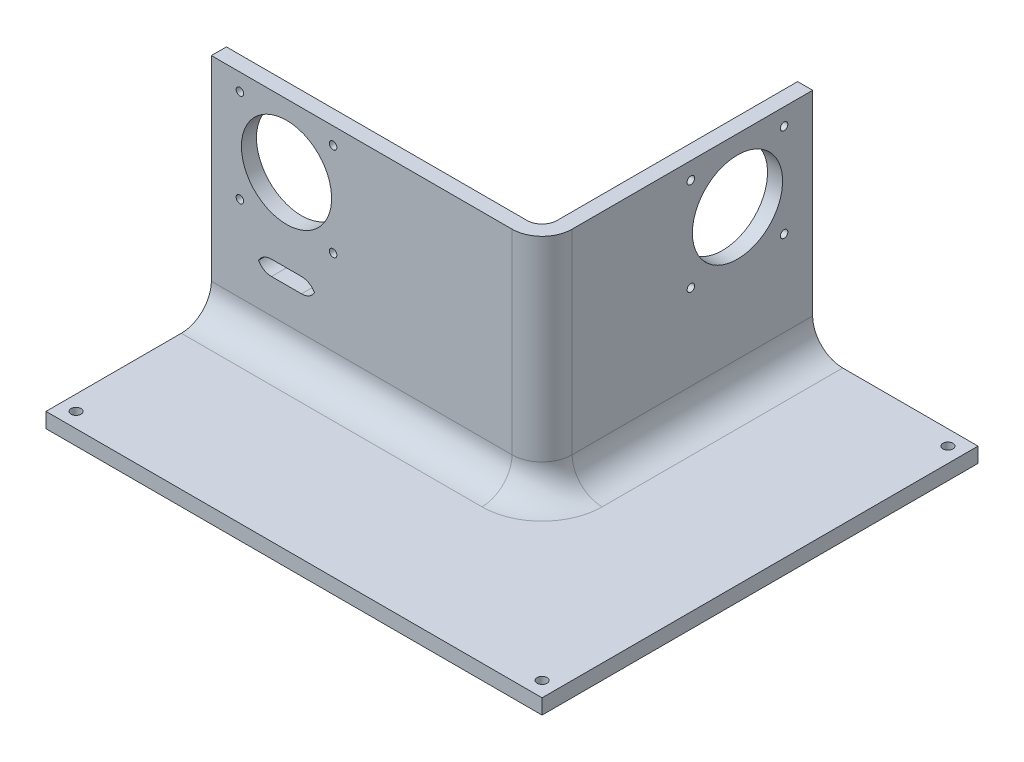
SolidWorks part; units mm, degrees
ref_plane "Front Plane" through (0, 0, 0) normal (0, 0, 1) x (1, 0, 0)
ref_plane "Top Plane" through (0, 0, 0) normal (0, 1, 0) x (1, 0, 0)
ref_plane "Right Plane" through (0, 0, 0) normal (1, 0, 0) x (0, 0, -1)
sketch "Sketch1" plane through (0, 0, 0) normal (0, 1, 0) x (1, 0, 0)
  line L0 (0, 85) -> (0, 0)
  line L1 (-105, -85) -> (105, -85)
  line L2 (-105, -85) -> (-105, 85)
  line L3 (-105, 85) -> (105, 85)
  line L4 (105, -85) -> (105, 85)
  line L5 (-105, -85) -> (105, 85) construction
  line L6 (-105, 85) -> (105, -85) construction
  line L7 (0, 0) -> (-105, 0)
  line L8 (-105, 0) -> (-105, -85)
  point P0 (0, 0)
  dimension "D1" = 170
  dimension "D2" = 210
extrude "Boss-Extrude1" add sketch "Sketch1" along normal blind 20 contours L0 L7 L2 L1 L4 L3 region at (17.5, 0, 14.1667)
sketch "Sketch2" plane through (0, 20, 0) normal (0, 1, 0) x (1, 0, 0)
  line L0 (0, 85) -> (105, 85) construction
  line L1 (0, 0) -> (5, 0)
  line L2 (0, 0) -> (0, 85)
  line L3 (0, 85) -> (5, 85)
  line L4 (5, 0) -> (5, 85)
  line L5 (0, 0) -> (5, 85) construction
  line L6 (0, 85) -> (5, 0) construction
  line L7 (0, 0) -> (-105, 0) construction
  line L8 (0, 85) -> (0, 0) construction
  point P0 (2.5, 42.5)
  dimension "D1" = 0
  dimension "D2" = 0
  dimension "D3" = 0
  dimension "D4" = 5
extrude "Boss-Extrude2" add sketch "Sketch2" along normal blind 60
sketch "Sketch3" plane through (0, 0, 0) normal (-1, 0, 0) x (0, 0, 1)
  line L0 (-85, 80) -> (0, 80) construction
  line L1 (-85, 80) -> (-85, 0) construction
  circle A0 centre (-60, 58.85) radius 15
  dimension "D3" = 30
  dimension "D1" = 21.15
  dimension "D2" = 25
extrude "Cut-Extrude1" cut sketch "Sketch3" against normal blind 100
sketch "Sketch4" plane through (0, 0, 0) normal (-1, 0, 0) x (0, 0, 1)
  circle A4 centre (-75.5, 74.35) radius 1.25
  circle A5 centre (-44.5, 74.35) radius 1.25
  circle A6 centre (-75.5, 43.35) radius 1.25
  circle A7 centre (-44.5, 43.35) radius 1.25
  circle A8 centre (-60, 58.85) radius 15 construction
  dimension "D1" = 0
  dimension "D3" = 0
  dimension "D6" = 2.5
  dimension "D9" = 2.5
  dimension "D12" = 0
  dimension "D7" = 2.5
  dimension "D8" = 2.5
  dimension "D10" = 15.5
  dimension "D2" = 31
  dimension "D4" = 31
  dimension "D5" = 31
  dimension "D11" = 15.5
extrude "Cut-Extrude2" cut sketch "Sketch4" against normal blind 100
sketch "Sketch7" plane through (0, 20, 0) normal (0, 1, 0) x (1, 0, 0)
  line L1 (-105, 0) -> (5, 0)
  line L2 (-105, 0) -> (-105, -5)
  line L3 (-105, -5) -> (5, -5)
  line L4 (5, 0) -> (5, -5)
  dimension "D1" = 5
  dimension "D2" = 0
extrude "Boss-Extrude6" add sketch "Sketch7" along normal blind 60
ref_plane "Plane2" through (-0.4878, 0, 0.6098) normal (-0.6247, 0, 0.7809) x (0.7809, 0, 0.6247)
fillet "Fillet3" radius 5 1 edges at (0, 40, 0)
sketch "Sketch8" plane through (0, 20, 0) normal (0, 1, 0) x (1, 0, 0)
  line L0 (-105, -85) -> (105, -85) construction
  line L1 (80, -85) -> (105, -85)
  line L2 (80, -85) -> (80, 85)
  line L3 (80, 85) -> (105, 85)
  line L4 (105, -85) -> (105, 85)
  line L5 (80, -85) -> (105, 85) construction
  line L6 (80, 85) -> (105, -85) construction
  line L7 (105, -60) -> (-105, -60)
  line L8 (105, -60) -> (105, -85)
  line L9 (105, -85) -> (-105, -85)
  line L10 (-105, -60) -> (-105, -85)
  line L11 (105, -60) -> (-105, -85) construction
  line L12 (105, -85) -> (-105, -60) construction
  point P0 (92.5, 0)
  point P6 (0, -72.5)
  line M7 (-105, -5) -> (-105, -85)
  line M8 (-105, -85) -> (105, -85)
  line M9 (105, -85) -> (105, 85)
  line M10 (105, 85) -> (5, 85)
  dimension "D1" = 0
  dimension "D2" = 0
  dimension "D3" = 25
  dimension "D4" = 25
extrude "Cut-Extrude3" cut sketch "Sketch8" against normal blind 100 contours L7 L4 L2 M10 | L7 L2 M9 M8 | L2 L7 M7 M8 region at (92.5, 20, 72.5) region at (-12.5, 20, 72.5) region at (92.5, 20, -12.5)
sketch "Sketch9" plane through (0, 20, 0) normal (0, 1, 0) x (1, 0, 0)
  line L0 (80, -60) -> (80, 85) construction
  line L1 (5, 85) -> (80, 85) construction
  line L2 (80, -60) -> (-105, -60) construction
  line L4 (-105, -60) -> (-105, -5) construction
  circle A0 centre (55, 80) radius 1.65
  circle A1 centre (55, -55) radius 1.65
  circle A2 centre (-100, -55) radius 1.65
  dimension "D3" = 3.3
  dimension "D6" = 3.3
  dimension "D8" = 3.3
  dimension "D1" = 25
  dimension "D2" = 5
  dimension "D4" = 0
  dimension "D5" = 5
  dimension "D7" = 0
  dimension "D9" = 5
extrude "Cut-Extrude4" cut sketch "Sketch9" against normal blind 100
sketch "Sketch10" plane through (0, 20, 0) normal (0, 1, 0) x (1, 0, 0)
  line L0 (-105, -5) -> (5, -5) construction
  line L1 (80, -60) -> (5, -60)
  line L2 (80, -60) -> (80, 85)
  line L3 (80, 85) -> (5, 85)
  line L4 (5, -60) -> (5, 85)
  line L5 (80, -60) -> (5, 85) construction
  line L6 (80, 85) -> (5, -60) construction
  line L7 (80, -5) -> (-105, -5)
  line L8 (80, -5) -> (80, -60)
  line L9 (80, -60) -> (-105, -60)
  line L10 (-105, -5) -> (-105, -60)
  line L11 (80, -5) -> (-105, -60) construction
  line L12 (80, -60) -> (-105, -5) construction
  line L13 (80, -60) -> (80, 85) construction
  point P0 (42.5, 12.5)
  point P6 (-12.5, -32.5)
  dimension "D1" = 0
  dimension "D2" = 0
  dimension "D3" = 0
  dimension "D4" = 0
extrude "Cut-Extrude5" cut sketch "Sketch10" against normal blind 15 contours L2 L1 L4 L3 | L8 L7 L10 L9
fillet "Fillet4" radius 10 3 edges at (5, 42.5, 5) (-50, 5, 5) (5, 5, -40)
sketch "Sketch11" plane through (0, 0, 5) normal (0, 0, 1) x (1, 0, 0)
  line L0 (-105, 80) -> (-105, 0) construction
  line L1 (-90, 26.35) -> (-70, 26.35)
  line L2 (-90, 26.35) -> (-90, 31.35)
  line L3 (-90, 31.35) -> (-70, 31.35)
  line L4 (-70, 26.35) -> (-70, 31.35)
  line L5 (-90, 26.35) -> (-70, 31.35) construction
  line L6 (-90, 31.35) -> (-70, 26.35) construction
  line L7 (-5, 0) -> (-105, 0) construction
  point P0 (-80, 28.85)
  point P9 (-47.5, 28.85)
  dimension "D1" = 25
  dimension "D2" = 28.85
  dimension "D3" = 5
  dimension "D4" = 20
extrude "Cut-Extrude6" cut sketch "Sketch11" against normal blind 6
fillet "Fillet5" radius 5 4 edges at (-90, 26.35, 2.5) (-90, 31.35, 2.5) (-70, 31.35, 2.5) (-70, 26.35, 2.5)
sketch "Sketch12" plane through (0, 0, 0) normal (0, 0, -1) x (-1, 0, 0)
  line L2 (5, 80) -> (105, 80) construction
  line L3 (105, 80) -> (105, 0) construction
  circle A0 centre (80, 58.85) radius 15
  circle A1 centre (95.5, 74.35) radius 1.25
  circle A2 centre (64.5, 74.35) radius 1.25
  circle A3 centre (64.5, 43.35) radius 1.25
  circle A4 centre (95.5, 43.35) radius 1.25
  dimension "D1" = 30
  dimension "D10" = 2.5
  dimension "D11" = 2.5
  dimension "D12" = 2.5
  dimension "D13" = 2.5
  dimension "D2" = 21.15
  dimension "D3" = 25
  dimension "D4" = 0
  dimension "D5" = 0
  dimension "D6" = 0
  dimension "D7" = 0
  dimension "D8" = 31
  dimension "D9" = 31
  dimension "D14" = 15.5
  dimension "D15" = 15.5
extrude "Cut-Extrude7" cut sketch "Sketch12" against normal blind 10
sketch "Sketch13" plane through (0, 5, 0) normal (0, 1, 0) x (1, 0, 0)
  line L0 (80, -60) -> (-105, -60) construction
  line L1 (80, 85) -> (60, 85)
  line L2 (80, 85) -> (80, -60)
  line L3 (80, -60) -> (60, -60)
  line L4 (60, 85) -> (60, -60)
  dimension "D1" = 20
extrude "Cut-Extrude8" cut sketch "Sketch13" against normal blind 10
